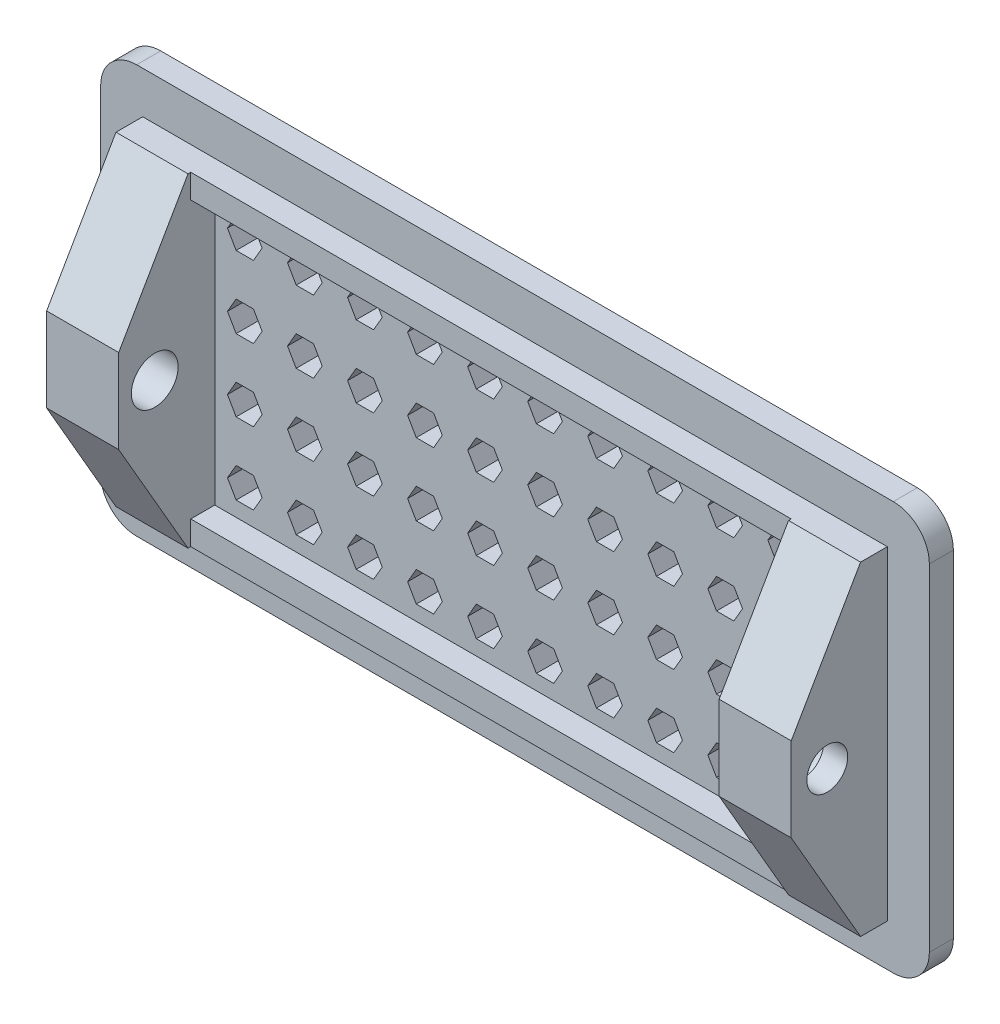
SolidWorks part; units mm, degrees
ref_plane "Přední rovina" through (0, 0, 0) normal (0, 0, 1) x (1, 0, 0)
ref_plane "Horní rovina" through (0, 0, 0) normal (0, 1, 0) x (1, 0, 0)
ref_plane "Pravá rovina" through (0, 0, 0) normal (1, 0, 0) x (0, 0, -1)
sketch "Skica1" plane through (0, 0, 0) normal (0, 0, 1) x (1, 0, 0)
  line L1 (-34.5, 17) -> (34.5, 17)
  line L2 (-34.5, 17) -> (-34.5, -17)
  line L3 (-34.5, -17) -> (34.5, -17)
  line L4 (34.5, 17) -> (34.5, -17)
  line L5 (-34.5, 17) -> (34.5, -17) construction
  line L6 (-34.5, -17) -> (34.5, 17) construction
  point P0 (0, 0)
  dimension "D1" = 69
  dimension "D2" = 34
extrude "Přidat vysunutím1" add sketch "Skica1" along normal blind 2
sketch "Skica2" plane through (0, 0, 2) normal (0, 0, 1) x (1, 0, 0)
  line L0 (-31, 13.5) -> (-31, -13.5)
  line L1 (-34.5, 17) -> (34.5, 17)
  line L2 (-34.5, 17) -> (-34.5, -17)
  line L3 (-34.5, -17) -> (34.5, -17)
  line L4 (34.5, 17) -> (34.5, -17)
  line L5 (-34.5, 17) -> (34.5, -17) construction
  line L6 (-34.5, -17) -> (34.5, 17) construction
  line L7 (-31, -13.5) -> (31, -13.5)
  line L8 (31, 13.5) -> (31, -13.5)
  line L9 (-31, 13.5) -> (31, 13.5)
  line L10 (-31, -13.5) -> (-25, -13.5)
  line L11 (-25, -13.5) -> (-25, 13.5)
  line L12 (0, 0) -> (0, 8.5655)
  line L13 (25, -13.5) -> (25, 13.5)
  line L14 (-25, 11.5) -> (25, 11.5)
  line L15 (0, 0) -> (-8.9395, 0)
  line L16 (-25, -11.5) -> (25, -11.5)
  point P0 (0, 0)
  dimension "D2" = 6
  dimension "D3" = 2
  dimension "D1" = 3.5
extrude "Přidat vysunutím2" add sketch "Skica2" along normal blind 2 contours L16 L11 L7 L13 | L11 L14 L13 L9 region at (0, 12.5, 2) region at (0, -12.5, 2)
extrude "Přidat vysunutím3" add sketch "Skica2<3>" along normal blind 8 contours L7 L11 L9 L0 | L13 L7 L8 L9 region at (-28, 0, 2) region at (28, 0, 2)
sketch "Skica2<3>" plane through (0, 0, 2) normal (0, 0, 1) x (1, 0, 0) same geometry as "Skica2"
sketch "Skica3" plane through (-25, 0, 0) normal (-1, 0, 0) x (0, 0, 1)
  line L0 (10, 0) -> (2, 0)
  line L1 (10, 13.5) -> (10, -13.5) construction
  line L2 (2, 13.5) -> (2, -13.5) construction
  point P6 (7, 0)
  dimension "D1" = 5
hole_wizard "Válcové zahloubení pro M3 šrouby s válcovou hlavou zaoblenou1" positions "Skica6" profile "Skica8" counterbore size "M3" standard "ANSI Metric" end condition up to next
sketch "Skica6" plane through (-25, 0, 0) normal (1, 0, 0) x (0, 0, -1)
  point P0 (-7, 0)
sketch "Skica8" plane through (-25, 0, 7) normal (0, 1, 0) x (0, 0, -1)
  line L0 (0, 0) -> (0, 6.001)
  line L1 (0, 6.001) -> (1.7, 6.001)
  line L3 (1.7, 6.001) -> (1.7, 4)
  line L4 (1.7, 4) -> (1.95, 4)
  line L5 (1.95, 4) -> (1.95, 0)
  line L7 (1.95, 0) -> (0, 0)
  line L11 (0, -6.35) -> (0, 107.95) construction
  dimension "Průměr díry skrz" = 3.4
  dimension "Hloubka díry skrz" = 6.001
  dimension "Průměr válcového zahloubení" = 3.9
  dimension "Hloubka válcového zahloubení" = 4
ref_plane "Rovina2" through (0, 0, 0) normal (1, 0, 0) x (0, 0, -1)
mirror "Zrcadlit1" about plane through (0, 0, 0) normal (1, 0, 0) of "Válcové zahloubení pro M3 šrouby s válcovou hlavou zaoblenou1"
chamfer "Zkosení1" distance 10 angle 30 2 edges at (28, 13.5, 10) (-28, 13.5, 10) first distance on face at (28, 0, 10) first distance on face at (-28, 0, 10)
ref_plane "Rovina3" through (0, 0, 0) normal (0, 1, 0) x (1, 0, 0)
chamfer "Zkosení2" distance 10 angle 30 2 edges at (28, -13.5, 10) (-28, -13.5, 10) first distance on face at (28, -5, 10) first distance on face at (-28, -5, 10)
fillet "Zaoblit1" radius 3 4 edges at (34.5, -17, 1) (-34.5, -17, 1) (-34.5, 17, 1) (34.5, 17, 1)
sketch "Skica9" plane through (0, 0, 2) normal (0, 0, 1) x (1, 0, 0)
  line L1 (-21.0566, -9) -> (-21.7783, -7.75)
  line L2 (-21.7783, -7.75) -> (-23.2217, -7.75)
  line L3 (-23.2217, -7.75) -> (-23.9434, -9)
  line L4 (-23.9434, -9) -> (-23.2217, -10.25)
  line L5 (-23.2217, -10.25) -> (-21.7783, -10.25)
  line L6 (-21.7783, -10.25) -> (-21.0566, -9)
  line L7 (-16.0566, -9) -> (-16.7783, -7.75)
  line L8 (-16.7783, -7.75) -> (-18.2217, -7.75)
  line L9 (-18.2217, -7.75) -> (-18.9434, -9)
  line L10 (-18.9434, -9) -> (-18.2217, -10.25)
  line L11 (-18.2217, -10.25) -> (-16.7783, -10.25)
  line L12 (-16.7783, -10.25) -> (-16.0566, -9)
  line L13 (-11.0566, -9) -> (-11.7783, -7.75)
  line L14 (-11.7783, -7.75) -> (-13.2217, -7.75)
  line L15 (-13.2217, -7.75) -> (-13.9434, -9)
  line L16 (-13.9434, -9) -> (-13.2217, -10.25)
  line L17 (-13.2217, -10.25) -> (-11.7783, -10.25)
  line L18 (-11.7783, -10.25) -> (-11.0566, -9)
  line L19 (-6.0566, -9) -> (-6.7783, -7.75)
  line L20 (-6.7783, -7.75) -> (-8.2217, -7.75)
  line L21 (-8.2217, -7.75) -> (-8.9434, -9)
  line L22 (-8.9434, -9) -> (-8.2217, -10.25)
  line L23 (-8.2217, -10.25) -> (-6.7783, -10.25)
  line L24 (-6.7783, -10.25) -> (-6.0566, -9)
  line L25 (-1.0566, -9) -> (-1.7783, -7.75)
  line L26 (-1.7783, -7.75) -> (-3.2217, -7.75)
  line L27 (-3.2217, -7.75) -> (-3.9434, -9)
  line L28 (-3.9434, -9) -> (-3.2217, -10.25)
  line L29 (-3.2217, -10.25) -> (-1.7783, -10.25)
  line L30 (-1.7783, -10.25) -> (-1.0566, -9)
  line L31 (3.9434, -9) -> (3.2217, -7.75)
  line L32 (3.2217, -7.75) -> (1.7783, -7.75)
  line L33 (1.7783, -7.75) -> (1.0566, -9)
  line L34 (1.0566, -9) -> (1.7783, -10.25)
  line L35 (1.7783, -10.25) -> (3.2217, -10.25)
  line L36 (3.2217, -10.25) -> (3.9434, -9)
  line L37 (8.9434, -9) -> (8.2217, -7.75)
  line L38 (8.2217, -7.75) -> (6.7783, -7.75)
  line L39 (6.7783, -7.75) -> (6.0566, -9)
  line L40 (6.0566, -9) -> (6.7783, -10.25)
  line L41 (6.7783, -10.25) -> (8.2217, -10.25)
  line L42 (8.2217, -10.25) -> (8.9434, -9)
  line L43 (13.9434, -9) -> (13.2217, -7.75)
  line L44 (13.2217, -7.75) -> (11.7783, -7.75)
  line L45 (11.7783, -7.75) -> (11.0566, -9)
  line L46 (11.0566, -9) -> (11.7783, -10.25)
  line L47 (11.7783, -10.25) -> (13.2217, -10.25)
  line L48 (13.2217, -10.25) -> (13.9434, -9)
  line L49 (18.9434, -9) -> (18.2217, -7.75)
  line L50 (18.2217, -7.75) -> (16.7783, -7.75)
  line L51 (16.7783, -7.75) -> (16.0566, -9)
  line L52 (16.0566, -9) -> (16.7783, -10.25)
  line L53 (16.7783, -10.25) -> (18.2217, -10.25)
  line L54 (18.2217, -10.25) -> (18.9434, -9)
  line L55 (23.9434, -9) -> (23.2217, -7.75)
  line L56 (23.2217, -7.75) -> (21.7783, -7.75)
  line L57 (21.7783, -7.75) -> (21.0566, -9)
  line L58 (21.0566, -9) -> (21.7783, -10.25)
  line L59 (21.7783, -10.25) -> (23.2217, -10.25)
  line L60 (23.2217, -10.25) -> (23.9434, -9)
  line L61 (-16.0566, -3) -> (-16.7783, -1.75)
  line L62 (-16.7783, -1.75) -> (-18.2217, -1.75)
  line L63 (-18.2217, -1.75) -> (-18.9434, -3)
  line L64 (-18.9434, -3) -> (-18.2217, -4.25)
  line L65 (-18.2217, -4.25) -> (-16.7783, -4.25)
  line L66 (-16.7783, -4.25) -> (-16.0566, -3)
  line L67 (-11.0566, -3) -> (-11.7783, -1.75)
  line L68 (-11.7783, -1.75) -> (-13.2217, -1.75)
  line L69 (-13.2217, -1.75) -> (-13.9434, -3)
  line L70 (-13.9434, -3) -> (-13.2217, -4.25)
  line L71 (-13.2217, -4.25) -> (-11.7783, -4.25)
  line L72 (-11.7783, -4.25) -> (-11.0566, -3)
  line L73 (-6.0566, -3) -> (-6.7783, -1.75)
  line L74 (-6.7783, -1.75) -> (-8.2217, -1.75)
  line L75 (-8.2217, -1.75) -> (-8.9434, -3)
  line L76 (-8.9434, -3) -> (-8.2217, -4.25)
  line L77 (-8.2217, -4.25) -> (-6.7783, -4.25)
  line L78 (-6.7783, -4.25) -> (-6.0566, -3)
  line L79 (-1.0566, -3) -> (-1.7783, -1.75)
  line L80 (-1.7783, -1.75) -> (-3.2217, -1.75)
  line L81 (-3.2217, -1.75) -> (-3.9434, -3)
  line L82 (-3.9434, -3) -> (-3.2217, -4.25)
  line L83 (-3.2217, -4.25) -> (-1.7783, -4.25)
  line L84 (-1.7783, -4.25) -> (-1.0566, -3)
  line L85 (3.9434, -3) -> (3.2217, -1.75)
  line L86 (3.2217, -1.75) -> (1.7783, -1.75)
  line L87 (1.7783, -1.75) -> (1.0566, -3)
  line L88 (1.0566, -3) -> (1.7783, -4.25)
  line L89 (1.7783, -4.25) -> (3.2217, -4.25)
  line L90 (3.2217, -4.25) -> (3.9434, -3)
  line L91 (8.9434, -3) -> (8.2217, -1.75)
  line L92 (8.2217, -1.75) -> (6.7783, -1.75)
  line L93 (6.7783, -1.75) -> (6.0566, -3)
  line L94 (6.0566, -3) -> (6.7783, -4.25)
  line L95 (6.7783, -4.25) -> (8.2217, -4.25)
  line L96 (8.2217, -4.25) -> (8.9434, -3)
  line L97 (13.9434, -3) -> (13.2217, -1.75)
  line L98 (13.2217, -1.75) -> (11.7783, -1.75)
  line L99 (11.7783, -1.75) -> (11.0566, -3)
  line L100 (11.0566, -3) -> (11.7783, -4.25)
  line L101 (11.7783, -4.25) -> (13.2217, -4.25)
  line L102 (13.2217, -4.25) -> (13.9434, -3)
  line L103 (18.9434, -3) -> (18.2217, -1.75)
  line L104 (18.2217, -1.75) -> (16.7783, -1.75)
  line L105 (16.7783, -1.75) -> (16.0566, -3)
  line L106 (16.0566, -3) -> (16.7783, -4.25)
  line L107 (16.7783, -4.25) -> (18.2217, -4.25)
  line L108 (18.2217, -4.25) -> (18.9434, -3)
  line L109 (23.9434, -3) -> (23.2217, -1.75)
  line L110 (23.2217, -1.75) -> (21.7783, -1.75)
  line L111 (21.7783, -1.75) -> (21.0566, -3)
  line L112 (21.0566, -3) -> (21.7783, -4.25)
  line L113 (21.7783, -4.25) -> (23.2217, -4.25)
  line L114 (23.2217, -4.25) -> (23.9434, -3)
  line L115 (-16.0566, 3) -> (-16.7783, 4.25)
  line L116 (-16.7783, 4.25) -> (-18.2217, 4.25)
  line L117 (-18.2217, 4.25) -> (-18.9434, 3)
  line L118 (-18.9434, 3) -> (-18.2217, 1.75)
  line L119 (-18.2217, 1.75) -> (-16.7783, 1.75)
  line L120 (-16.7783, 1.75) -> (-16.0566, 3)
  line L121 (-11.0566, 3) -> (-11.7783, 4.25)
  line L122 (-11.7783, 4.25) -> (-13.2217, 4.25)
  line L123 (-13.2217, 4.25) -> (-13.9434, 3)
  line L124 (-13.9434, 3) -> (-13.2217, 1.75)
  line L125 (-13.2217, 1.75) -> (-11.7783, 1.75)
  line L126 (-11.7783, 1.75) -> (-11.0566, 3)
  line L127 (-6.0566, 3) -> (-6.7783, 4.25)
  line L128 (-6.7783, 4.25) -> (-8.2217, 4.25)
  line L129 (-8.2217, 4.25) -> (-8.9434, 3)
  line L130 (-8.9434, 3) -> (-8.2217, 1.75)
  line L131 (-8.2217, 1.75) -> (-6.7783, 1.75)
  line L132 (-6.7783, 1.75) -> (-6.0566, 3)
  line L133 (-1.0566, 3) -> (-1.7783, 4.25)
  line L134 (-1.7783, 4.25) -> (-3.2217, 4.25)
  line L135 (-3.2217, 4.25) -> (-3.9434, 3)
  line L136 (-3.9434, 3) -> (-3.2217, 1.75)
  line L137 (-3.2217, 1.75) -> (-1.7783, 1.75)
  line L138 (-1.7783, 1.75) -> (-1.0566, 3)
  line L139 (3.9434, 3) -> (3.2217, 4.25)
  line L140 (3.2217, 4.25) -> (1.7783, 4.25)
  line L141 (1.7783, 4.25) -> (1.0566, 3)
  line L142 (1.0566, 3) -> (1.7783, 1.75)
  line L143 (1.7783, 1.75) -> (3.2217, 1.75)
  line L144 (3.2217, 1.75) -> (3.9434, 3)
  line L145 (8.9434, 3) -> (8.2217, 4.25)
  line L146 (8.2217, 4.25) -> (6.7783, 4.25)
  line L147 (6.7783, 4.25) -> (6.0566, 3)
  line L148 (6.0566, 3) -> (6.7783, 1.75)
  line L149 (6.7783, 1.75) -> (8.2217, 1.75)
  line L150 (8.2217, 1.75) -> (8.9434, 3)
  line L151 (13.9434, 3) -> (13.2217, 4.25)
  line L152 (13.2217, 4.25) -> (11.7783, 4.25)
  line L153 (11.7783, 4.25) -> (11.0566, 3)
  line L154 (11.0566, 3) -> (11.7783, 1.75)
  line L155 (11.7783, 1.75) -> (13.2217, 1.75)
  line L156 (13.2217, 1.75) -> (13.9434, 3)
  line L157 (18.9434, 3) -> (18.2217, 4.25)
  line L158 (18.2217, 4.25) -> (16.7783, 4.25)
  line L159 (16.7783, 4.25) -> (16.0566, 3)
  line L160 (16.0566, 3) -> (16.7783, 1.75)
  line L161 (16.7783, 1.75) -> (18.2217, 1.75)
  line L162 (18.2217, 1.75) -> (18.9434, 3)
  line L163 (23.9434, 3) -> (23.2217, 4.25)
  line L164 (23.2217, 4.25) -> (21.7783, 4.25)
  line L165 (21.7783, 4.25) -> (21.0566, 3)
  line L166 (21.0566, 3) -> (21.7783, 1.75)
  line L167 (21.7783, 1.75) -> (23.2217, 1.75)
  line L168 (23.2217, 1.75) -> (23.9434, 3)
  line L169 (-16.0566, 9) -> (-16.7783, 10.25)
  line L170 (-16.7783, 10.25) -> (-18.2217, 10.25)
  line L171 (-18.2217, 10.25) -> (-18.9434, 9)
  line L172 (-18.9434, 9) -> (-18.2217, 7.75)
  line L173 (-18.2217, 7.75) -> (-16.7783, 7.75)
  line L174 (-16.7783, 7.75) -> (-16.0566, 9)
  line L175 (-11.0566, 9) -> (-11.7783, 10.25)
  line L176 (-11.7783, 10.25) -> (-13.2217, 10.25)
  line L177 (-13.2217, 10.25) -> (-13.9434, 9)
  line L178 (-13.9434, 9) -> (-13.2217, 7.75)
  line L179 (-13.2217, 7.75) -> (-11.7783, 7.75)
  line L180 (-11.7783, 7.75) -> (-11.0566, 9)
  line L181 (-6.0566, 9) -> (-6.7783, 10.25)
  line L182 (-6.7783, 10.25) -> (-8.2217, 10.25)
  line L183 (-8.2217, 10.25) -> (-8.9434, 9)
  line L184 (-8.9434, 9) -> (-8.2217, 7.75)
  line L185 (-8.2217, 7.75) -> (-6.7783, 7.75)
  line L186 (-6.7783, 7.75) -> (-6.0566, 9)
  line L187 (-1.0566, 9) -> (-1.7783, 10.25)
  line L188 (-1.7783, 10.25) -> (-3.2217, 10.25)
  line L189 (-3.2217, 10.25) -> (-3.9434, 9)
  line L190 (-3.9434, 9) -> (-3.2217, 7.75)
  line L191 (-3.2217, 7.75) -> (-1.7783, 7.75)
  line L192 (-1.7783, 7.75) -> (-1.0566, 9)
  line L193 (3.9434, 9) -> (3.2217, 10.25)
  line L194 (3.2217, 10.25) -> (1.7783, 10.25)
  line L195 (1.7783, 10.25) -> (1.0566, 9)
  line L196 (1.0566, 9) -> (1.7783, 7.75)
  line L197 (1.7783, 7.75) -> (3.2217, 7.75)
  line L198 (3.2217, 7.75) -> (3.9434, 9)
  line L199 (8.9434, 9) -> (8.2217, 10.25)
  line L200 (8.2217, 10.25) -> (6.7783, 10.25)
  line L201 (6.7783, 10.25) -> (6.0566, 9)
  line L202 (6.0566, 9) -> (6.7783, 7.75)
  line L203 (6.7783, 7.75) -> (8.2217, 7.75)
  line L204 (8.2217, 7.75) -> (8.9434, 9)
  line L205 (13.9434, 9) -> (13.2217, 10.25)
  line L206 (13.2217, 10.25) -> (11.7783, 10.25)
  line L207 (11.7783, 10.25) -> (11.0566, 9)
  line L208 (11.0566, 9) -> (11.7783, 7.75)
  line L209 (11.7783, 7.75) -> (13.2217, 7.75)
  line L210 (13.2217, 7.75) -> (13.9434, 9)
  line L211 (18.9434, 9) -> (18.2217, 10.25)
  line L212 (18.2217, 10.25) -> (16.7783, 10.25)
  line L213 (16.7783, 10.25) -> (16.0566, 9)
  line L214 (16.0566, 9) -> (16.7783, 7.75)
  line L215 (16.7783, 7.75) -> (18.2217, 7.75)
  line L216 (18.2217, 7.75) -> (18.9434, 9)
  line L217 (23.9434, 9) -> (23.2217, 10.25)
  line L218 (23.2217, 10.25) -> (21.7783, 10.25)
  line L219 (21.7783, 10.25) -> (21.0566, 9)
  line L220 (21.0566, 9) -> (21.7783, 7.75)
  line L221 (21.7783, 7.75) -> (23.2217, 7.75)
  line L222 (23.2217, 7.75) -> (23.9434, 9)
  line L223 (-21.0566, -3) -> (-21.7783, -1.75)
  line L224 (-21.7783, -1.75) -> (-23.2217, -1.75)
  line L225 (-23.2217, -1.75) -> (-23.9434, -3)
  line L226 (-23.9434, -3) -> (-23.2217, -4.25)
  line L227 (-23.2217, -4.25) -> (-21.7783, -4.25)
  line L228 (-21.7783, -4.25) -> (-21.0566, -3)
  line L229 (-21.0566, 3) -> (-21.7783, 4.25)
  line L230 (-21.7783, 4.25) -> (-23.2217, 4.25)
  line L231 (-23.2217, 4.25) -> (-23.9434, 3)
  line L232 (-23.9434, 3) -> (-23.2217, 1.75)
  line L233 (-23.2217, 1.75) -> (-21.7783, 1.75)
  line L234 (-21.7783, 1.75) -> (-21.0566, 3)
  line L235 (-21.0566, 9) -> (-21.7783, 10.25)
  line L236 (-21.7783, 10.25) -> (-23.2217, 10.25)
  line L237 (-23.2217, 10.25) -> (-23.9434, 9)
  line L238 (-23.9434, 9) -> (-23.2217, 7.75)
  line L239 (-23.2217, 7.75) -> (-21.7783, 7.75)
  line L240 (-21.7783, 7.75) -> (-21.0566, 9)
  circle A0 centre (-22.5, -9) radius 1.25 construction
  circle A1 centre (-17.5, -9) radius 1.25 construction
  circle A2 centre (-12.5, -9) radius 1.25 construction
  circle A3 centre (-7.5, -9) radius 1.25 construction
  circle A4 centre (-2.5, -9) radius 1.25 construction
  circle A5 centre (2.5, -9) radius 1.25 construction
  circle A6 centre (7.5, -9) radius 1.25 construction
  circle A7 centre (12.5, -9) radius 1.25 construction
  circle A8 centre (17.5, -9) radius 1.25 construction
  circle A9 centre (22.5, -9) radius 1.25 construction
  circle A10 centre (-17.5, -3) radius 1.25 construction
  circle A11 centre (-12.5, -3) radius 1.25 construction
  circle A12 centre (-7.5, -3) radius 1.25 construction
  circle A13 centre (-2.5, -3) radius 1.25 construction
  circle A14 centre (2.5, -3) radius 1.25 construction
  circle A15 centre (7.5, -3) radius 1.25 construction
  circle A16 centre (12.5, -3) radius 1.25 construction
  circle A17 centre (17.5, -3) radius 1.25 construction
  circle A18 centre (22.5, -3) radius 1.25 construction
  circle A19 centre (-17.5, 3) radius 1.25 construction
  circle A20 centre (-12.5, 3) radius 1.25 construction
  circle A21 centre (-7.5, 3) radius 1.25 construction
  circle A22 centre (-2.5, 3) radius 1.25 construction
  circle A23 centre (2.5, 3) radius 1.25 construction
  circle A24 centre (7.5, 3) radius 1.25 construction
  circle A25 centre (12.5, 3) radius 1.25 construction
  circle A26 centre (17.5, 3) radius 1.25 construction
  circle A27 centre (22.5, 3) radius 1.25 construction
  circle A28 centre (-17.5, 9) radius 1.25 construction
  circle A29 centre (-12.5, 9) radius 1.25 construction
  circle A30 centre (-7.5, 9) radius 1.25 construction
  circle A31 centre (-2.5, 9) radius 1.25 construction
  circle A32 centre (2.5, 9) radius 1.25 construction
  circle A33 centre (7.5, 9) radius 1.25 construction
  circle A34 centre (12.5, 9) radius 1.25 construction
  circle A35 centre (17.5, 9) radius 1.25 construction
  circle A36 centre (22.5, 9) radius 1.25 construction
  circle A37 centre (-22.5, -3) radius 1.25 construction
  circle A38 centre (-22.5, 3) radius 1.25 construction
  circle A39 centre (-22.5, 9) radius 1.25 construction
  dimension "D1" = 2.5
  dimension "D2" = 2.5
  dimension "D3" = 2.5
  dimension "D4" = 10
  dimension "D5" = 4
extrude "Odebrat vysunutím1" cut sketch "Skica9" against normal blind 10
